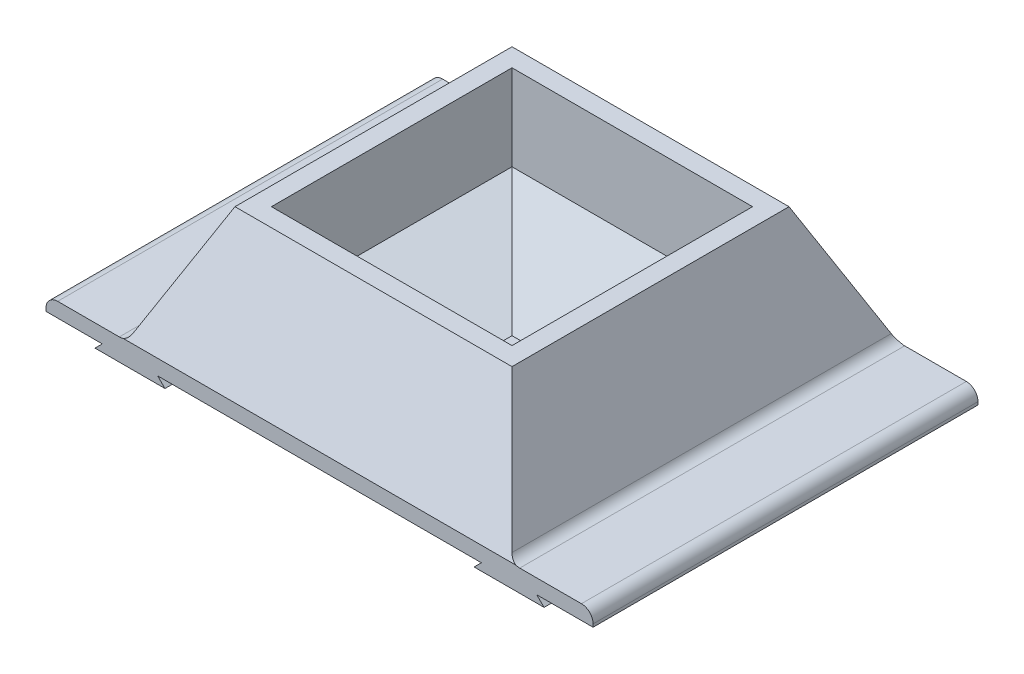
SolidWorks part; units mm, degrees
ref_plane "Front Plane" through (0, 0, 0) normal (0, 0, 1) x (1, 0, 0)
ref_plane "Top Plane" through (0, 0, 0) normal (0, 1, 0) x (1, 0, 0)
ref_plane "Right Plane" through (0, 0, 0) normal (1, 0, 0) x (0, 0, -1)
sketch "Sketch1" plane through (0, 0, 0) normal (0, 1, 0) x (1, 0, 0)
  line L1 (-119.126, -83.82) -> (119.126, -83.82)
  line L2 (-119.126, -83.82) -> (-119.126, 83.82)
  line L3 (-119.126, 83.82) -> (119.126, 83.82)
  line L4 (119.126, -83.82) -> (119.126, 83.82)
  line L5 (-119.126, -83.82) -> (119.126, 83.82) construction
  line L6 (-119.126, 83.82) -> (119.126, -83.82) construction
  point P0 (0, 0)
  dimension "D1" = 167.64
  dimension "D2" = 238.252
extrude "Boss-Extrude1" add sketch "Sketch1" along normal blind 6.35
sketch "Sketch2" plane through (0, 6.35, 0) normal (0, 1, 0) x (1, 0, 0)
  line L1 (-52.3875, -52.3875) -> (52.3875, -52.3875)
  line L2 (-52.3875, -52.3875) -> (-52.3875, 52.3875)
  line L3 (-52.3875, 52.3875) -> (52.3875, 52.3875)
  line L4 (52.3875, -52.3875) -> (52.3875, 52.3875)
  line L5 (-52.3875, -52.3875) -> (52.3875, 52.3875) construction
  line L6 (-52.3875, 52.3875) -> (52.3875, -52.3875) construction
  line L7 (60.325, -60.325) -> (-60.325, -60.325)
  line L8 (60.325, -60.325) -> (60.325, 60.325)
  line L9 (60.325, 60.325) -> (-60.325, 60.325)
  line L10 (-60.325, -60.325) -> (-60.325, 60.325)
  line L11 (60.325, -60.325) -> (-60.325, 60.325) construction
  line L12 (60.325, 60.325) -> (-60.325, -60.325) construction
  point P0 (0, 0)
  point P6 (0, 0)
  dimension "D1" = 104.775
  dimension "D2" = 104.775
  dimension "D3" = 120.65
  dimension "D4" = 120.65
extrude "Boss-Extrude2" add sketch "Sketch2" along normal blind 50.8
chamfer "Chamfer1" distance 23.622 distance2 50.8 4 edges at (0, 6.35, 60.325) (60.325, 6.35, 0) (-60.325, 6.35, 0) (0, 6.35, -60.325) first distance on face at (0, 6.35, 0)
chamfer "Chamfer2" distance 13.462 angle 75 4 edges at (0, 6.35, -52.3875) (52.3875, 6.35, 0) (-52.3875, 6.35, 0) (0, 6.35, 52.3875) first distance on face at (0, 31.75, -52.3875) first distance on face at (52.3875, 31.75, 0) first distance on face at (-52.3875, 31.75, 0) first distance on face at (0, 31.75, 52.3875)
sketch "Sketch3" plane through (0, 0, -83.82) normal (0, 0, -1) x (-1, 0, 0)
  line L0 (94.615, 0) -> (70.485, 0)
  line L1 (-119.126, 0) -> (119.126, 0) construction
  line L2 (94.615, 0) -> (97.79, -3.175)
  line L3 (97.79, -3.175) -> (67.31, -3.175)
  line L4 (67.31, -3.175) -> (70.485, 0)
  line L5 (0, 31.4325) -> (0, -31.4325) construction
  line L6 (-67.31, -3.175) -> (-70.485, 0)
  line L7 (-97.79, -3.175) -> (-67.31, -3.175)
  line L8 (-94.615, 0) -> (-97.79, -3.175)
  line L9 (-94.615, 0) -> (-70.485, 0)
  point P4 (82.55, 0)
  dimension "D1" = 24.13
  dimension "D2" = 82.55
  dimension "D3" = 45
  dimension "D4" = 3.175
  dimension "D5" = 45
extrude "Boss-Extrude3" add sketch "Sketch3" against normal up to surface (167.64 mm away) up to face at (0, 4.8308, 83.82)
fillet "Fillet1" radius 5.08 4 edges at (119.126, 6.35, 0) (-119.126, 6.35, 0) (-83.947, 6.35, 0) (83.947, 6.35, 0)
